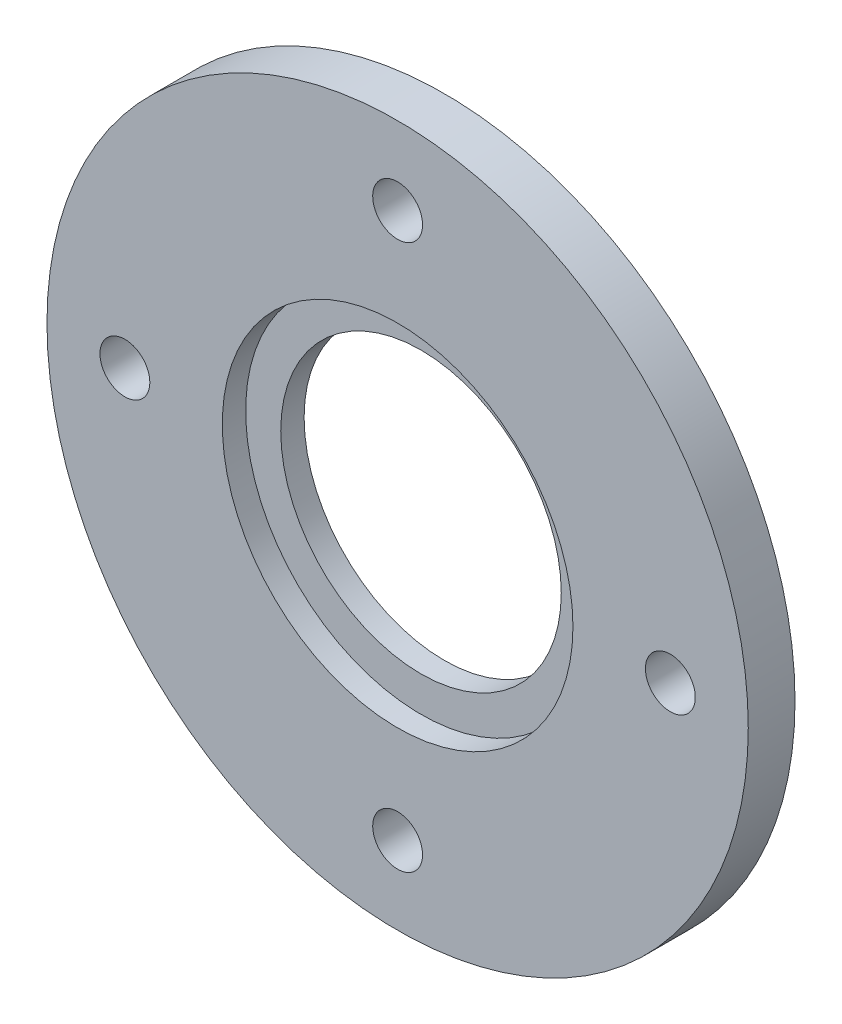
SolidWorks part; units mm, degrees
ref_plane "正面" through (0, 0, 0) normal (0, 0, 1) x (1, 0, 0)
ref_plane "平面" through (0, 0, 0) normal (0, 1, 0) x (1, 0, 0)
ref_plane "右側面" through (0, 0, 0) normal (1, 0, 0) x (0, 0, -1)
sketch "ｽｹｯﾁ1" plane through (0, 0, 0) normal (0, 0, 1) x (1, 0, 0)
  line L0 (0, 0) -> (-17.5, 0) construction
  circle A0 centre (0, 0) radius 9
  circle A1 centre (-17.5, 0) radius 1.6 construction
  circle A2 centre (0, 0) radius 22.5
  dimension "D1" = 17.5
  dimension "D2" = 18
  dimension "D3" = 3.2
  dimension "D4" = 45
extrude "ﾎﾞｽ - 押し出し1" add sketch "ｽｹｯﾁ1" along normal blind 3
sketch "ｽｹｯﾁ2" plane through (0, 0, 3) normal (0, 0, 1) x (1, 0, 0)
  circle A0 centre (-17.5, 0) radius 1.6
  circle A1 centre (-17.5, 0) radius 1.6 construction
extrude "ｶｯﾄ - 押し出し1" cut sketch "ｽｹｯﾁ2" against normal through all
pattern_circular "円形ﾊﾟﾀｰﾝ2" count 4 over 360 about axis through (0, 0, 3) along (0, 0, -1) of "ｶｯﾄ - 押し出し1"
sketch "ｽｹｯﾁ3" plane through (0, 0, 3) normal (0, 0, 1) x (1, 0, 0)
  circle A0 centre (0, 0) radius 11.25
  circle A1 centre (0, 0) radius 9
  circle A2 centre (0, 0) radius 9 construction
  dimension "D1" = 22.5
extrude "ｶｯﾄ - 押し出し2" cut sketch "ｽｹｯﾁ3" against normal blind 1.5
